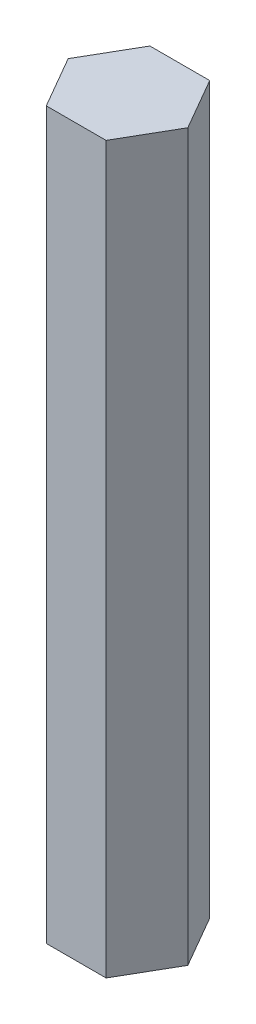
SolidWorks part; units mm, degrees
ref_plane "Front" through (0, 0, 0) normal (0, 0, 1) x (1, 0, 0)
ref_plane "Top" through (0, 0, 0) normal (0, 1, 0) x (1, 0, 0)
ref_plane "Right" through (0, 0, 0) normal (1, 0, 0) x (0, 0, -1)
sketch "Sketch1" plane through (0, 0, 0) normal (0, 1, 0) x (1, 0, 0)
  line L1 (7.3323, 0) -> (3.6662, 6.35)
  line L2 (3.6662, 6.35) -> (-3.6662, 6.35)
  line L3 (-3.6662, 6.35) -> (-7.3323, 0)
  line L4 (-7.3323, 0) -> (-3.6662, -6.35)
  line L5 (-3.6662, -6.35) -> (3.6662, -6.35)
  line L6 (3.6662, -6.35) -> (7.3323, 0)
  circle A0 centre (0, 0) radius 6.35 construction
  dimension "D1" = 12.7
extrude "Boss-Extrude1" add sketch "Sketch1" along normal blind 88.9
ref_axis "Axis1" through (0, 50, 0) along (0, -1, 0)
